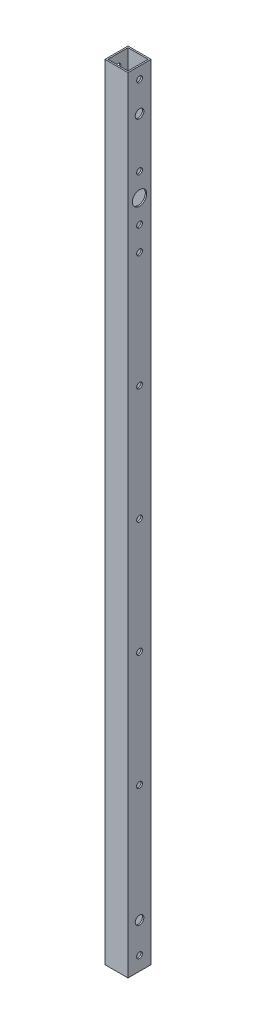
SolidWorks part; units mm, degrees
ref_plane "Front Plane" through (0, 0, 0) normal (0, 0, 1) x (1, 0, 0)
ref_plane "Top Plane" through (0, 0, 0) normal (0, 1, 0) x (1, 0, 0)
ref_plane "Right Plane" through (0, 0, 0) normal (1, 0, 0) x (0, 0, -1)
sketch "Sketch1" plane through (0, 0, 0) normal (0, 1, 0) x (1, 0, 0)
  line L1 (-12.7, -12.7) -> (12.7, -12.7)
  line L2 (-12.7, -12.7) -> (-12.7, 12.7)
  line L3 (-12.7, 12.7) -> (12.7, 12.7)
  line L4 (12.7, -12.7) -> (12.7, 12.7)
  line L5 (-12.7, -12.7) -> (12.7, 12.7) construction
  line L6 (-12.7, 12.7) -> (12.7, -12.7) construction
  line L7 (-11.1125, -11.1125) -> (11.1125, -11.1125)
  line L8 (-11.1125, -11.1125) -> (-11.1125, 11.1125)
  line L9 (-11.1125, 11.1125) -> (11.1125, 11.1125)
  line L10 (11.1125, -11.1125) -> (11.1125, 11.1125)
  line L11 (-11.1125, -11.1125) -> (11.1125, 11.1125) construction
  line L12 (-11.1125, 11.1125) -> (11.1125, -11.1125) construction
  point P0 (0, 0)
  point P6 (0, 0)
  dimension "D1" = 25.4
  dimension "D2" = 1.5875
extrude "Boss-Extrude1" add sketch "Sketch1" along normal blind 863.6
hole_wizard "1/4 (0.25) Diameter Hole1" positions "Sketch2" profile "Sketch3" hole size "1/4" standard "ANSI Inch" end condition through all
sketch "Sketch2" plane through (12.7, 0, 0) normal (1, 0, 0) x (0, 0, -1)
  line L0 (0, 863.6) -> (0, 0) construction
  line L1 (-12.7, 863.6) -> (12.7, 863.6) construction
  line L2 (-12.7, 0) -> (12.7, 0) construction
  point P8 (0, 850.9)
  point P10 (0, 15.3983)
  point P17 (0, 431.8)
  point P19 (0, 558.8)
  point P21 (0, 685.8)
  point P23 (0, 304.8)
  point P25 (0, 177.8)
  dimension "D1" = 12.7
  dimension "D2" = 127
  dimension "D3" = 127
  dimension "D4" = 127
  dimension "D5" = 127
sketch "Sketch3" plane through (12.7, 177.8, 0) normal (0, 1, 0) x (0, 0, -1)
  line L0 (0, 0) -> (0, 25.4)
  line L1 (0, 25.4) -> (3.175, 25.4)
  line L2 (3.175, 25.4) -> (3.175, 0)
  line L5 (3.175, 0) -> (0, 0)
  line L11 (0, -6.35) -> (0, 107.95) construction
  dimension "Thru Hole Dia." = 6.35
  dimension "Thru Hole Depth" = 25.4
ref_point "Point1"
ref_point "Point2"
ref_axis "Axis1" through (12.7, 863.6, 0) along (0, -1, 0)
hole_wizard "3/8 (0.375) Diameter Hole1" positions "Sketch6" profile "Sketch7" hole size "3/8" standard "ANSI Inch" end condition through all
sketch "Sketch6" plane through (12.7, 0, 0) normal (1, 0, 0) x (0, 0, -1)
  line L1 (0, 863.6) -> (0, 0) construction
  point P9 (0, 818.045)
  point P11 (0, 48.9006)
sketch "Sketch7" plane through (12.7, 48.9006, 0) normal (0, 1, 0) x (0, 0, -1)
  line L0 (0, 0) -> (0, 25.4)
  line L1 (0, 25.4) -> (4.7625, 25.4)
  line L2 (4.7625, 25.4) -> (4.7625, 0)
  line L5 (4.7625, 0) -> (0, 0)
  line L11 (0, -6.35) -> (0, 107.95) construction
  dimension "Thru Hole Dia." = 9.525
  dimension "Thru Hole Depth" = 25.4
hole_wizard "5/8 (0.625) Diameter Hole1" positions "Sketch8" profile "Sketch9" hole size "5/8" standard "ANSI Inch" end condition through all
sketch "Sketch8" plane through (12.7, 0, 0) normal (1, 0, 0) x (0, 0, -1)
  line L0 (0, 863.6) -> (0, 0) construction
  point P6 (0, 737.7108)
sketch "Sketch9" plane through (12.7, 737.7108, 0) normal (0, 1, 0) x (0, 0, -1)
  line L0 (0, 0) -> (0, 25.4)
  line L1 (0, 25.4) -> (7.9375, 25.4)
  line L2 (7.9375, 25.4) -> (7.9375, 0)
  line L5 (7.9375, 0) -> (0, 0)
  line L11 (0, -6.35) -> (0, 107.95) construction
  dimension "Thru Hole Dia." = 15.875
  dimension "Thru Hole Depth" = 25.4
hole_wizard "1/4 (0.25) Diameter Hole2" positions "Sketch10" profile "Sketch11" hole size "1/4" standard "ANSI Inch" end condition through all
sketch "Sketch10" plane through (12.7, 0, 0) normal (1, 0, 0) x (0, 0, -1)
  line L0 (0, 818.045) -> (0, 685.8) construction
  point P7 (0, 763.1108)
  point P9 (0, 712.3108)
  point P13 (0, 712.3108)
  point P15 (0, 763.1108)
sketch "Sketch11" plane through (12.7, 712.3108, 0) normal (0, 1, 0) x (0, 0, -1)
  line L0 (0, 0) -> (0, 25.4)
  line L1 (0, 25.4) -> (3.175, 25.4)
  line L2 (3.175, 25.4) -> (3.175, 0)
  line L5 (3.175, 0) -> (0, 0)
  line L11 (0, -6.35) -> (0, 107.95) construction
  dimension "Thru Hole Dia." = 6.35
  dimension "Thru Hole Depth" = 25.4
